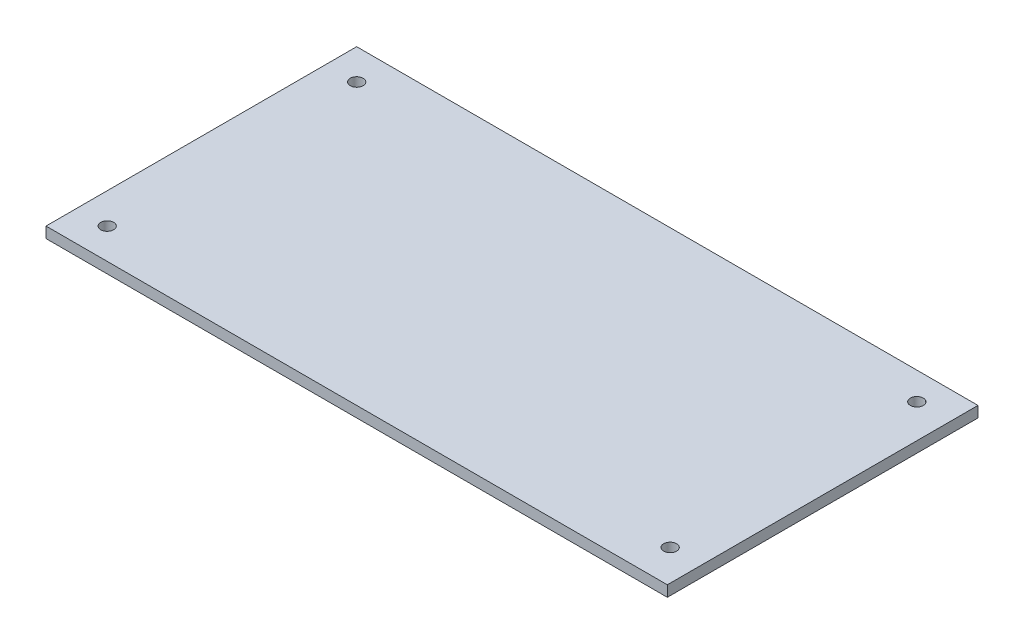
SolidWorks part; units mm, degrees
ref_plane "Front Plane" through (0, 0, 0) normal (0, 0, 1) x (1, 0, 0)
ref_plane "Top Plane" through (0, 0, 0) normal (0, 1, 0) x (1, 0, 0)
ref_plane "Right Plane" through (0, 0, 0) normal (1, 0, 0) x (0, 0, -1)
sketch "Sketch1" plane through (0, 0, 0) normal (0, 1, 0) x (1, 0, 0)
  line L1 (-216.1549, 23.7753) -> (88.6451, 23.7753)
  line L2 (-216.1549, 23.7753) -> (-216.1549, -128.6247)
  line L3 (-216.1549, -128.6247) -> (88.6451, -128.6247)
  line L4 (88.6451, 23.7753) -> (88.6451, -128.6247)
  dimension "D1" = 304.8
  dimension "D2" = 152.4
extrude "Boss-Extrude1" add sketch "Sketch1" along normal blind 5.334
sketch "Sketch2" plane through (0, 5.334, 0) normal (0, 1, 0) x (1, 0, 0)
  line L0 (-216.1549, -128.6247) -> (88.6451, -128.6247) construction
  line L1 (-216.1549, 23.7753) -> (-216.1549, -128.6247) construction
  line L2 (-64.6105, 23.7753) -> (-63.7549, -128.6247) construction
  line L3 (88.6451, 23.7753) -> (-216.1549, 23.7753) construction
  line L4 (-216.1549, -52.4247) -> (88.6451, -52.4247) construction
  line L5 (88.6451, -128.6247) -> (88.6451, 23.7753) construction
  circle A0 centre (-201.1549, -113.6247) radius 3.175
  circle A1 centre (-201.1549, 8.7753) radius 3.175
  circle A2 centre (73.468, -112.0829) radius 3.175
  circle A3 centre (72.0937, 10.3094) radius 3.175
  dimension "D1" = 15
  dimension "D3" = 6.35
  dimension "D2" = 15
extrude "Cut-Extrude1" cut sketch "Sketch2" against normal blind 10
